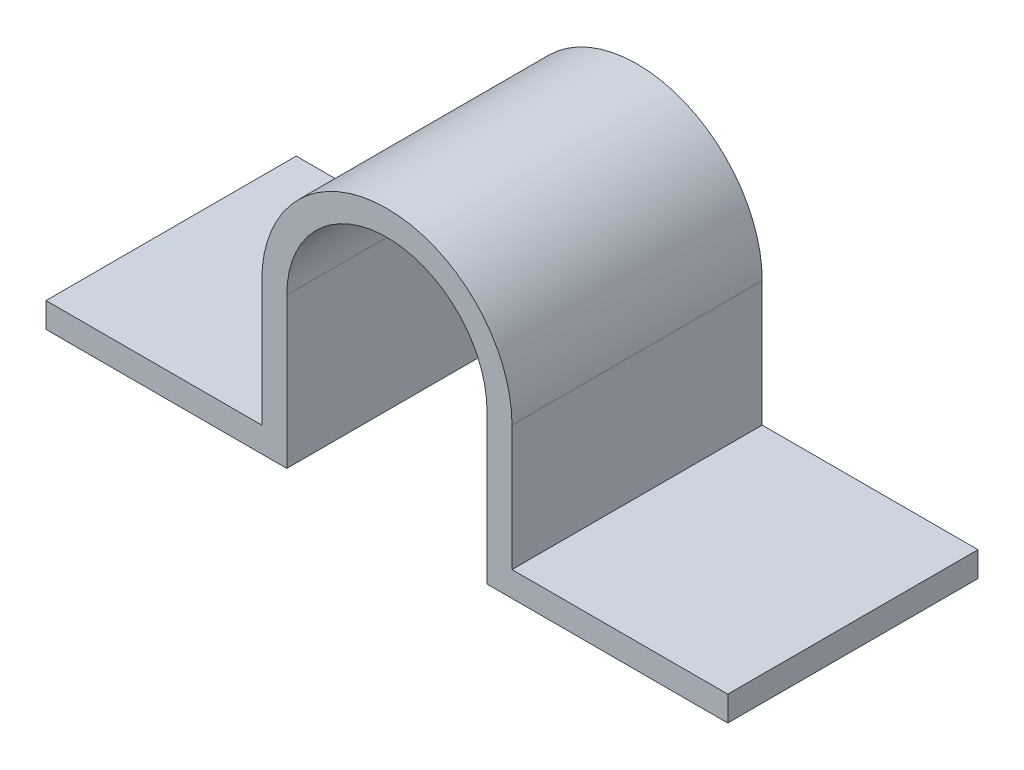
SolidWorks part; units mm, degrees
material "镀铬不锈钢"
ref_plane "前视基准面" through (0, 0, 0) normal (0, 0, 1) x (1, 0, 0)
ref_plane "上视基准面" through (0, 0, 0) normal (0, 1, 0) x (1, 0, 0)
ref_plane "右视基准面" through (0, 0, 0) normal (1, 0, 0) x (0, 0, -1)
sketch "草图1" plane through (0, 0, 0) normal (0, 0, 1) x (1, 0, 0)
  line L0 (0, 0) -> (0, 16.5455) construction
  line L1 (5, 6) -> (5, 1)
  line L2 (5, 1) -> (13.6233, 1)
  line L3 (13.6233, 1) -> (13.6233, 0)
  line L4 (13.6233, 0) -> (4, 0)
  line L5 (4, 6) -> (4, 0)
  line L6 (0, 0) -> (18.8515, 0) construction
  line L7 (-4, 6) -> (-4, 0)
  line L8 (-13.6233, 0) -> (-4, 0)
  line L9 (-13.6233, 1) -> (-13.6233, 0)
  line L10 (-5, 1) -> (-13.6233, 1)
  line L11 (-5, 6) -> (-5, 1)
  arc A0 (5, 6) -> (-5, 6) centre (0, 6) ccw
  arc A1 (4, 6) -> (-4, 6) centre (0, 6) ccw
  point P4 (4, 0)
  dimension "D1" = 10
  dimension "D2" = 1
  dimension "D3" = 1
  dimension "D4" = 6
extrude "凸台-拉伸1" add sketch "草图1" along normal blind 10 contours A1 L7 L8 L9 L10 L11 A0 L1 L2 L3 L4 L5
